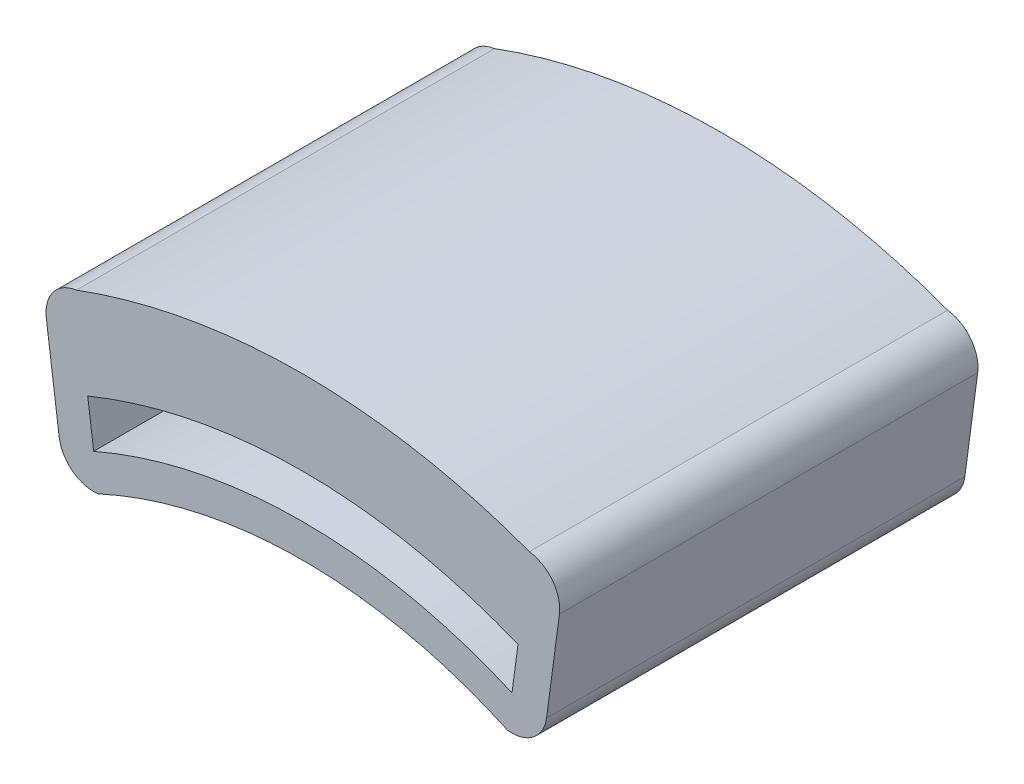
SolidWorks part; units mm, degrees
ref_plane "Front Plane" through (0, 0, 0) normal (0, 0, 1) x (1, 0, 0)
ref_plane "Top Plane" through (0, 0, 0) normal (0, 1, 0) x (1, 0, 0)
ref_plane "Right Plane" through (0, 0, 0) normal (1, 0, 0) x (0, 0, -1)
sketch "Sketch1" plane through (0, 0, 0) normal (0, 0, 1) x (1, 0, 0)
  line L0 (13.2294, 36.7301) -> (12.2963, 29.7209) construction
  line L1 (-13.2416, 36.8223) -> (-12.3085, 29.8131) construction
  line L2 (-13, 35.0072) -> (-12.3431, 30.0727)
  line L3 (13, 35.0072) -> (12.3431, 30.0727)
  line L4 (11.7361, 25.5129) -> (12, 27.4955)
  line L5 (-10, 35.0072) -> (10, 35.0072) construction
  line L6 (-10, 35.0072) -> (-10, 32.5072) construction
  line L7 (-10, 32.5072) -> (10, 32.5072) construction
  line L8 (10, 35.0072) -> (10, 32.5072) construction
  line L9 (-11.7361, 25.5129) -> (-12, 27.4955)
  circle A0 centre (0, 0) radius 30 construction
  arc A1 (-12, 27.4955) -> (12, 27.4955) centre (0, 0) cw
  arc A2 (-13, 35.0072) -> (13, 35.0072) centre (0, 0) cw
  arc A3 (-12.3431, 30.0727) -> (12.3431, 30.0727) centre (0, 0) cw
  arc A4 (-11.7361, 25.5129) -> (11.7361, 25.5129) centre (0, 0) cw
  point P7 (0, 37.3431)
  point P9 (0, 30)
  point P21 (0, 32.5072)
  dimension "D1" = 60
  dimension "D2" = 24
  dimension "D3" = 26
  dimension "D4" = 2.6
  dimension "D5" = 2
  dimension "D6" = 0
  dimension "D7" = 20
  dimension "D8" = 2.5
  dimension "D9" = 32.5072
extrude "Boss-Extrude1" add sketch "Sketch1" along normal blind 24
ref_plane "Plane1" through (0, 32.51, 0) normal (0, 1, 0) x (1, 0, 0)
sketch "Sketch4" plane through (0, 32.51, 0) normal (0, 1, 0) x (1, 0, 0)
  line L0 (0, -24) -> (0, 0) construction
  line L1 (-13, -24) -> (13, -24) construction
  line L2 (-13, -12) -> (13, -12) construction
  line L3 (-13, -24) -> (-13, 0) construction
  line L4 (13, -24) -> (13, 0) construction
  circle A0 centre (0, -12) radius 10
extrude "Cut-Extrude1" cut sketch "Sketch4" along normal blind 2.5 and the other way up to next
sketch "Sketch5" plane through (-8.1945, -1.0909, 0) normal (-0.9913, -0.132, 0) x (0, 0, 1)
  line L0 (0, 36.4166) -> (0, 26.8385)
  line L1 (0, -6.5066) -> (0, 6.5066) construction
  line L2 (24, 36.4166) -> (0, 36.4166) construction
  line L3 (24, 26.8385) -> (0, 26.8385) construction
  line L4 (0, 26.8385) -> (24, 26.8385)
  line L5 (24, 26.8385) -> (24, 36.4166)
  line L6 (24, 36.4166) -> (0, 36.4166)
extrude "Boss-Extrude2" add sketch "Sketch5" along normal blind 2
sketch "Sketch6" plane through (8.1945, -1.0909, 0) normal (0.9913, -0.132, 0) x (0, 0, -1)
  line L0 (-24, 36.4166) -> (-24, 26.8385)
  line L1 (-24, 26.8385) -> (0, 26.8385)
  line L2 (0, 6.6517) -> (0, -6.6517) construction
  line L3 (-24, 26.8385) -> (0, 26.8385) construction
  line L4 (0, 26.8385) -> (0, 36.4166)
  line L5 (-24, 36.4166) -> (0, 36.4166) construction
  line L6 (0, 36.4166) -> (-24, 36.4166)
extrude "Boss-Extrude3" add sketch "Sketch6" along normal blind 2
fillet "Fillet1" radius 2 4 edges at (-14.9825, 34.7433, 12) (-13.7186, 25.249, 12) (13.7186, 25.249, 12) (14.9825, 34.7433, 12)
